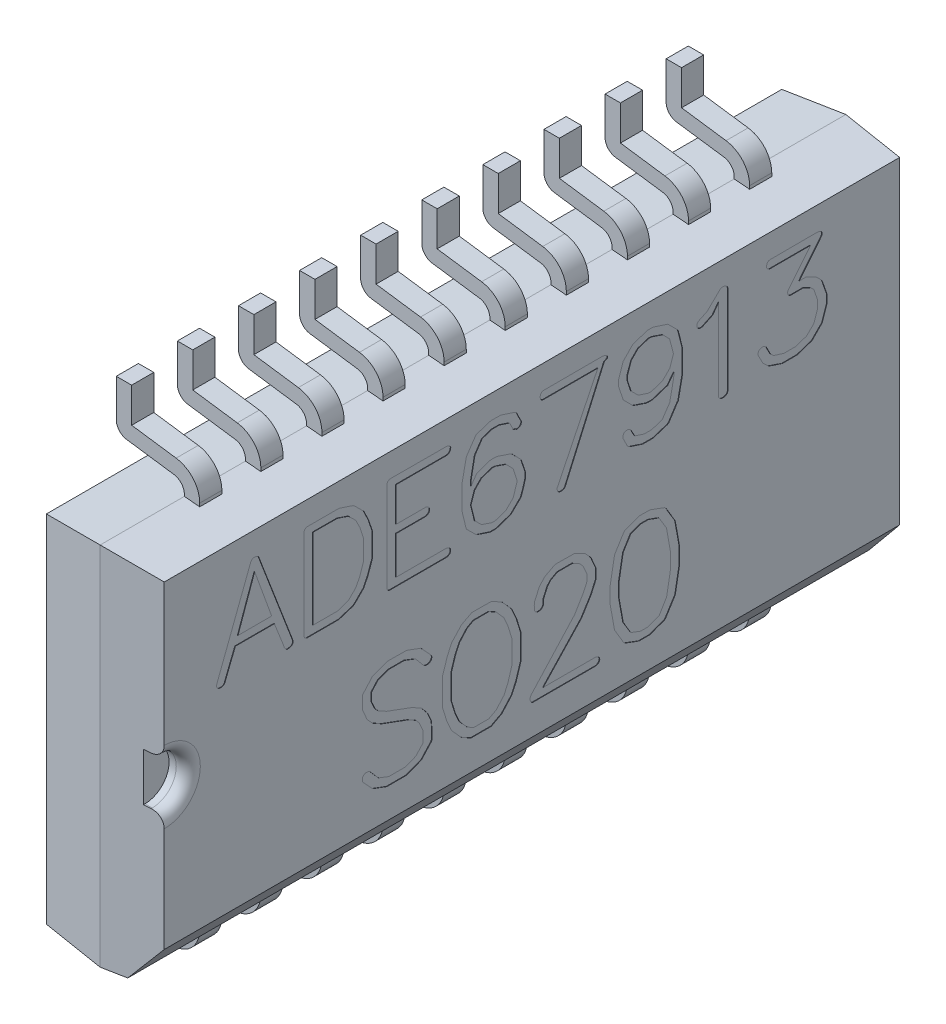
SolidWorks part; units mm, degrees
ref_plane "Front Plane" through (0, 0, 0) normal (0, 0, 1) x (1, 0, 0)
ref_plane "Top Plane" through (0, 0, 0) normal (0, 1, 0) x (1, 0, 0)
ref_plane "Right Plane" through (0, 0, 0) normal (1, 0, 0) x (0, 0, -1)
sketch "Sketch1" plane through (0, 0, 0) normal (1, 0, 0) x (0, 0, -1)
  line L1 (-7.75, 3.8) -> (7.75, 3.8)
  line L2 (-7.75, 3.8) -> (-7.75, -3.8)
  line L3 (-7.75, -3.8) -> (7.75, -3.8)
  line L4 (7.75, 3.8) -> (7.75, -3.8)
  line L5 (-7.75, 3.8) -> (7.75, -3.8) construction
  line L6 (-7.75, -3.8) -> (7.75, 3.8) construction
  point P0 (0, 0)
  dimension "D1" = 7.6
  dimension "D2" = 15.5
extrude "Boss-Extrude1" add sketch "Sketch1" along normal mid plane 2.45 draft 5
chamfer "Chamfer1" distance 0.7 angle 45 1 edges at (1.225, -3.6928, 0)
sketch "Sketch3" plane through (1.225, 0, 0) normal (1, 0, 0) x (0, 0, -1)
  line L0 (-7.6428, 3.6928) -> (-7.6428, -2.9228) construction
  line L1 (-7.6428, 0.5) -> (-7.8928, 0.5)
  line L2 (-7.8928, 0.5) -> (-7.8928, -0.5)
  line L3 (-7.8928, -0.5) -> (-7.6428, -0.5)
  arc A0 (-7.6428, 0.5) -> (-7.6428, -0.5) centre (-7.6428, 0) cw
  dimension "D1" = 0.5
  dimension "D2" = 0.25
extrude "Cut-Extrude1" cut sketch "Sketch3" against normal blind 0.4
fillet "Fillet1" radius 0.25 1 edges at (1.225, 0, 7.1428)
sketch "Sketch5" plane through (0, 0, 0) normal (0, 0, 1) x (1, 0, 0)
  line L0 (0, 3.4486) -> (0, 3.8388)
  line L1 (0, 3.8) -> (0, -3.8) construction
  line L2 (-0.2152, 4.0864) -> (-1.1998, 4.2248)
  line L3 (-1.415, 4.4723) -> (-1.415, 5.255)
  line L4 (1.225, 3.6928) -> (1.225, 0.75) construction
  line L5 (0, 0) -> (3.3608, 0) construction
  arc A0 (-1.415, 4.4723) -> (-1.1998, 4.2248) centre (-1.165, 4.4723) ccw
  arc A1 (-0.2152, 4.0864) -> (0, 3.8388) centre (-0.25, 3.8388) cw
  point P14 (-1.415, 4.255)
  dimension "D5" = 0.25
  dimension "D1" = 2.64
  dimension "D2" = 10.51
  dimension "D3" = 1
  dimension "D4" = 98
extrude "Extrude-Thin1" add sketch "Sketch5" against normal blind 0.46 from offset 6 separate body thin
pattern_linear "LPattern1" count 10 spacing 1.27 along (0, 0, -1) of bodies 103
mirror "Mirror1" about plane through (0, 0, 0) normal (0, 1, 0) of bodies 103 104 105 106 107 108 109 110 111 112
sketch "Sketch8" plane through (1.225, 0, 0) normal (1, 0, 0) x (0, 0, -1)
  line L0 (-7.2771, 1.25) -> (7.2771, 1.25) construction
  line L1 (-7.2771, -2.25) -> (7.2771, -2.25) construction
  text T0 "ADE67913" font "SWSimp" height 2
  text T1 "SO20\r\n\r\n" font "SWSimp" height 2.25
  point P3 (0, 1.25)
  point P5 (0, 0)
  point P8 (0, -2.25)
  point P9 (0, 0)
  dimension "D1" = 1.25
  dimension "D2" = 2.25
extrude "Cut-Extrude2" cut sketch "Sketch8" against normal blind 0.01
